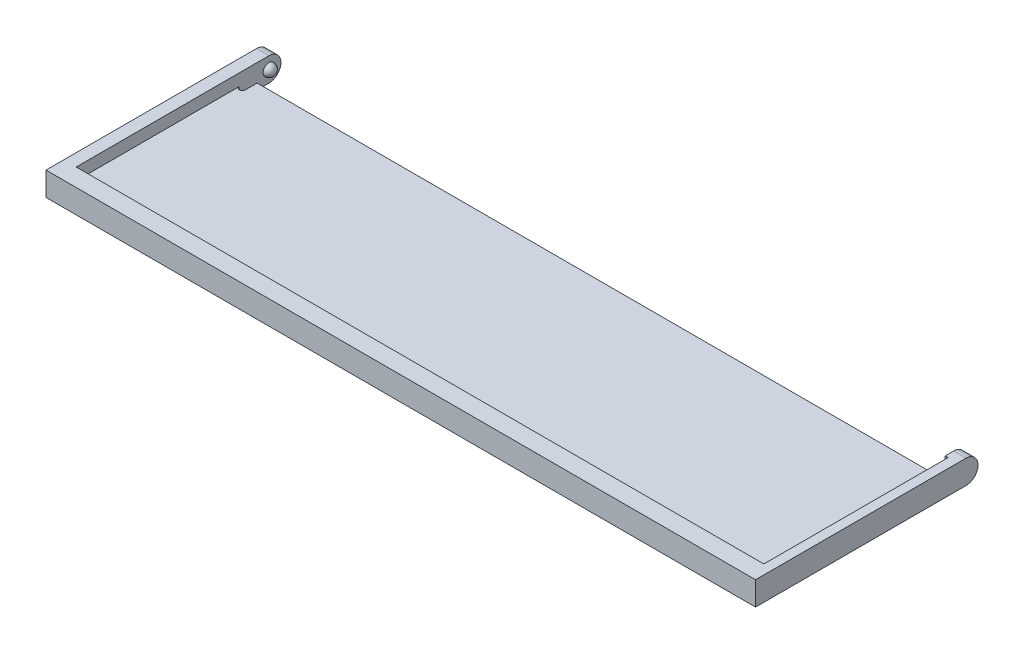
SolidWorks part; units mm, degrees
ref_plane "Alzado" through (0, 0, 0) normal (0, 0, 1) x (1, 0, 0)
ref_plane "Planta" through (0, 0, 0) normal (0, 1, 0) x (1, 0, 0)
ref_plane "Vista lateral" through (0, 0, 0) normal (1, 0, 0) x (0, 0, -1)
sketch "Croquis1" plane through (0, 0, 0) normal (0, 1, 0) x (1, 0, 0)
  line L1 (-65.5839, 30.0544) -> (49.8161, 30.0544)
  line L2 (-67.6839, 30.0544) -> (-67.6839, -4.4456)
  line L3 (-67.6839, -4.4456) -> (51.9161, -4.4456)
  line L4 (51.9161, 30.0544) -> (51.9161, -4.4456)
  line L6 (-67.6839, 30.0544) -> (-67.6839, 33.0544)
  line L7 (-67.6839, 33.0544) -> (-65.5839, 33.0544)
  line L8 (-65.5839, 30.0544) -> (-65.5839, 33.0544)
  line L10 (51.9161, 30.0544) -> (51.9161, 33.0544)
  line L11 (51.9161, 33.0544) -> (49.8161, 33.0544)
  line L12 (49.8161, 30.0544) -> (49.8161, 33.0544)
  dimension "D1" = 119.6
  dimension "D2" = 34.5
  dimension "D3" = 2.1
  dimension "D4" = 3
  dimension "D5" = 3
  dimension "D6" = 2.1
extrude "Saliente-Extruir1" add sketch "Croquis1" along normal blind 4
sketch "Croquis2" plane through (49.8161, 0, 0) normal (-1, 0, 0) x (0, 0, 1)
  line L0 (-33.0544, 4) -> (-33.0544, 0) construction
  line L1 (-33.0544, 4) -> (-30.0544, 4) construction
  line L2 (-32.0544, 2) -> (-30.0544, 2) construction
  line L3 (-32.0544, 2) -> (-30.0544, 2)
  arc A0 (-32.0544, 2) -> (-30.0544, 2) centre (-31.0544, 2) ccw
  dimension "D1" = 2
  dimension "D2" = 2
  dimension "D3" = 2
sketch "Croquis3" plane through (-65.5839, 0, 0) normal (1, 0, 0) x (0, 0, -1)
  line L0 (30.0544, 4) -> (33.0544, 4) construction
  line L1 (33.0544, 4) -> (33.0544, 0) construction
  line L2 (32.0544, 2) -> (30.0544, 2) construction
  line L3 (32.0544, 2) -> (30.0544, 2)
  arc A0 (30.0544, 2) -> (32.0544, 2) centre (31.0544, 2) ccw
  dimension "D1" = 2
  dimension "D2" = 2
  dimension "D3" = 2
sketch "Croquis4" plane through (0, 4, 0) normal (0, 1, 0) x (1, 0, 0)
  line L0 (49.8161, 30.0544) -> (49.8161, 26.0544)
  line L1 (48.8161, 30.0544) -> (48.8161, 26.0544)
  line L2 (49.8161, 30.0544) -> (-65.5839, 30.0544) construction
  line L3 (49.8161, 30.0544) -> (48.8161, 30.0544)
  line L4 (-65.5839, 30.0544) -> (-65.5839, 26.0544)
  line L5 (-64.5839, 30.0544) -> (-64.5839, 26.0544)
  line L6 (-65.5839, 30.0544) -> (-64.5839, 30.0544)
  line L8 (-64.5839, 30.0544) -> (48.8161, 30.0544)
  line L9 (-64.5839, 30.0544) -> (-64.5839, 28.0544)
  line L10 (-64.5839, 28.0544) -> (48.8161, 28.0544)
  line L11 (48.8161, 30.0544) -> (48.8161, 28.0544)
  arc A0 (48.8161, 26.0544) -> (49.8161, 26.0544) centre (49.3161, 26.0544) ccw
  arc A1 (-65.5839, 26.0544) -> (-64.5839, 26.0544) centre (-65.0839, 26.0544) ccw
  line M10 (49.8161, 30.0544) -> (-65.5839, 30.0544)
  dimension "D1" = 4
  dimension "D2" = 1
  dimension "D3" = 4
  dimension "D4" = 1
  dimension "D5" = 2
extrude "Cortar-Extruir1" cut sketch "Croquis4" against normal blind 10 contours L5 L10 L1 M10 | L1 A0 L0 M10 | L4 A1 L5 M10 region at (49.3161, 4, -27.8567) region at (-7.8839, 4, -29.0544) region at (-65.0839, 4, -27.8567)
fillet "Redondeo1" radius 2 4 edges at (-66.6339, 0, -33.0544) (-66.6339, 4, -33.0544) (50.8661, 0, -33.0544) (50.8661, 4, -33.0544)
revolve "Revolución1" add sketch "Croquis3" angle 360 about L2
revolve "Revolución2" add sketch "Croquis2" angle 360 about L2
sketch "Croquis5" plane through (0, 4, 0) normal (0, 1, 0) x (1, 0, 0)
  line L0 (-65.5839, 26.0544) -> (-65.5839, 31.0544) construction
  line L1 (-65.5839, 29.6257) -> (50.3161, 29.6257)
  line L2 (-65.5839, 29.6257) -> (-65.5839, -1.4456)
  line L3 (-65.5839, -1.4456) -> (50.3161, -1.4456)
  line L4 (50.3161, 29.6257) -> (50.3161, -1.4456)
  line L5 (-67.6839, -4.4456) -> (51.9161, -4.4456) construction
  dimension "D1" = 3
extrude "Cortar-Extruir2" cut sketch "Croquis5" against normal blind 2
